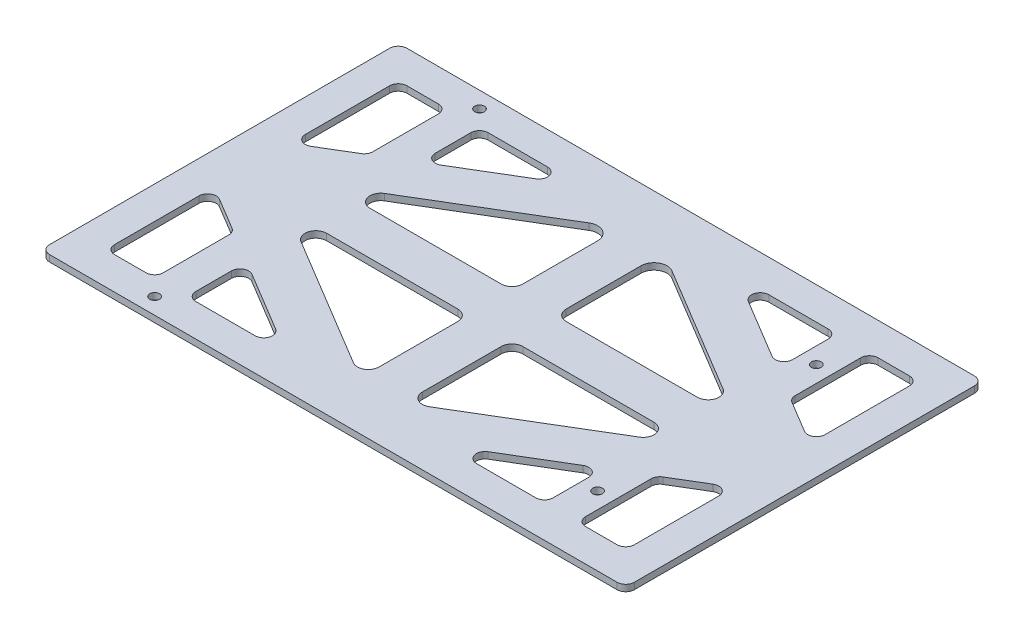
SolidWorks part; units mm, degrees
ref_plane "Alzado" through (0, 0, 0) normal (0, 0, 1) x (1, 0, 0)
ref_plane "Planta" through (0, 0, 0) normal (0, 1, 0) x (1, 0, 0)
ref_plane "Vista lateral" through (0, 0, 0) normal (1, 0, 0) x (0, 0, -1)
sketch "Croquis1" plane through (0, 0, 0) normal (0, 1, 0) x (1, 0, 0)
  line L1 (135, -82.5) -> (-135, -82.5)
  line L2 (135, -82.5) -> (135, 82.5)
  line L3 (135, 82.5) -> (-135, 82.5)
  line L4 (-135, -82.5) -> (-135, 82.5)
  line L5 (135, -82.5) -> (-135, 82.5) construction
  line L6 (135, 82.5) -> (-135, -82.5) construction
  point P0 (0, 0)
  dimension "D1" = 165
  dimension "D2" = 270
extrude "Saliente-Extruir1" add sketch "Croquis1" along normal blind 3
fillet "Redondeo1" radius 4 4 edges at (-135, 1.5, -82.5) (135, 1.5, -82.5) (135, 1.5, 82.5) (-135, 1.5, 82.5)
sketch "Croquis2" plane through (0, 3, 0) normal (0, 1, 0) x (1, 0, 0)
  line L0 (131, 82.5) -> (-131, 82.5) construction
  line L1 (135, -78.5) -> (135, 78.5) construction
  circle A0 centre (90, 50.5) radius 2.25
  dimension "D1" = 4.5
  dimension "D2" = 32
  dimension "D3" = 45
extrude "Cortar-Extruir1" cut sketch "Croquis2" against normal through all
mirror "Simetría1" about plane through (0, 0, 0) normal (0, 0, 1) of "Cortar-Extruir1"
sketch "Croquis3" plane through (0, 3, 0) normal (0, 1, 0) x (1, 0, 0)
  line L0 (-135, 78.5) -> (-135, -78.5) construction
  line L1 (131, 82.5) -> (-131, 82.5) construction
  line L2 (-135, 0) -> (-113.8944, 0) construction
  circle A0 centre (-90, 75) radius 2.25
  circle A1 centre (-90, -75) radius 2.25
  dimension "D1" = 4.5
  dimension "D2" = 45
  dimension "D3" = 7.5
extrude "Cortar-Extruir2" cut sketch "Croquis3" against normal through all
sketch "Croquis4" plane through (0, 3, 0) normal (0, 1, 0) x (1, 0, 0)
  line L0 (0, 82.5) -> (0, -82.5) construction
  line L1 (131, 82.5) -> (-131, 82.5) construction
  line L2 (-131, -82.5) -> (131, -82.5) construction
  line L3 (-135, 0) -> (135, 0) construction
  line L4 (-135, 78.5) -> (-135, -78.5) construction
  line L5 (135, -78.5) -> (135, 78.5) construction
  line L6 (0, -82.5) -> (131, -82.5) construction
  line L7 (135, -82.5) -> (135, 78.5) construction
  line L8 (131, 82.5) -> (0, 82.5) construction
  line L9 (116, 67.5) -> (101.5, 67.5)
  line L12 (110.2817, 0) -> (2.6409, -64.5845) construction
  line L13 (131, 67.5) -> (-131, 67.5) construction
  line L14 (4.9275, 63.2125) -> (110.2817, 0) construction
  line L15 (15, 10) -> (75.5635, 10)
  line L16 (131, 82.5) -> (-131, 82.5) construction
  line L17 (15, -10) -> (75.5635, -10)
  line L18 (10, 49.5719) -> (10, 15)
  line L19 (19.087, 54.7169) -> (78.136, 19.2875)
  line L20 (78.136, -19.2875) -> (17.5725, -55.6256)
  line L24 (49.038, 60.07) -> (76.442, 43.6276)
  line L29 (15.2174, 80.3624) -> (149.1548, 0) construction
  line L30 (90, 50.5) -> (90, 67.5) construction
  line L31 (149.1548, 0) -> (12.9308, -81.7344) construction
  line L32 (99.442, 29.8276) -> (113.942, 21.1276)
  line L34 (82.5, 63.5) -> (82.5, 47.0576)
  line L36 (97.5, 63.5) -> (97.5, 33.2576)
  line L37 (120, 24.5576) -> (120, 63.5)
  line L38 (78.5, 67.5) -> (51.096, 67.5)
  line L39 (10, -15) -> (10, -51.3381)
  arc A0 (78.5, 67.5) -> (82.5, 63.5) centre (78.5, 63.5) cw
  arc A1 (82.5, 47.0576) -> (76.442, 43.6276) centre (78.5, 47.0576) cw
  arc A2 (49.038, 60.07) -> (51.096, 67.5) centre (51.096, 63.5) cw
  arc A3 (120, 63.5) -> (116, 67.5) centre (116, 63.5) ccw
  arc A4 (120, 24.5576) -> (113.942, 21.1276) centre (116, 24.5576) cw
  arc A5 (99.442, 29.8276) -> (97.5, 33.2576) centre (101.5, 33.2576) cw
  arc A6 (101.5, 67.5) -> (97.5, 63.5) centre (101.5, 63.5) ccw
  arc A7 (10, -51.3381) -> (17.5725, -55.6256) centre (15, -51.3381) ccw
  arc A9 (10, 49.5719) -> (19.087, 54.7169) centre (16, 49.5719) cw
  arc A10 (75.5635, 10) -> (78.136, 19.2875) centre (75.5635, 15) ccw
  arc A11 (75.5635, -10) -> (78.136, -19.2875) centre (75.5635, -15) cw
  arc A12 (15, 10) -> (10, 15) centre (15, 15) cw
  arc A13 (15, -10) -> (10, -15) centre (15, -15) ccw
  point P44 (97.5, 30.9929)
  point P64 (10, -10)
  dimension "D5" = 4
  dimension "D6" = 4
  dimension "D7" = 5
  dimension "D13" = 5
  dimension "D14" = 5
  dimension "D2" = 22.43
  dimension "D4" = 15
  dimension "D8" = 15
  dimension "D9" = 38.8724
  dimension "D10" = 10
  dimension "D11" = 10
  dimension "D12" = 10
  dimension "D1" = 15
  dimension "D3" = 20
extrude "Cortar-Extruir3" cut sketch "Croquis4" against normal through all
mirror "Simetría2" about plane through (0, 0, 0) normal (0, 0, 1) of face at (117.4709, 1.5, -21.9597) of face at (106.692, 1.5, -25.4776) of face at (98.2451, 1.5, -31.4147) of face at (97.5, 1.5, -48.3788) of face at (99.0858, 1.5, -65.9142) of face at (108.75, 1.5, -67.5) of face at (118.4142, 1.5, -65.9142) of face at (120, 1.5, -44.0288) of face at (80.9142, 1.5, -65.9142) of face at (82.5, 1.5, -55.2788) of face at (79.9709, 1.5, -44.4597) of face at (62.74, 1.5, -51.8488) of face at (48.6541, 1.5, -64.1764) of face at (64.798, 1.5, -67.5)
mirror "Simetría4" about plane through (0, 0, 0) normal (1, 0, 0) of "Cortar-Extruir3"
mirror "Simetría6" about plane through (0, 0, 0) normal (0, 0, 1) of face at (-64.798, 1.5, -67.5) of face at (-48.6541, 1.5, -64.1764) of face at (-62.74, 1.5, -51.8488) of face at (-79.9709, 1.5, -44.4597) of face at (-80.9142, 1.5, -65.9142) of face at (-82.5, 1.5, -55.2788) of face at (-97.5, 1.5, -48.3788) of face at (-98.2451, 1.5, -31.4147) of face at (-106.692, 1.5, -25.4776) of face at (-117.4709, 1.5, -21.9597) of face at (-120, 1.5, -44.0288) of face at (-99.0858, 1.5, -65.9142) of face at (-118.4142, 1.5, -65.9142) of face at (-108.75, 1.5, -67.5)
